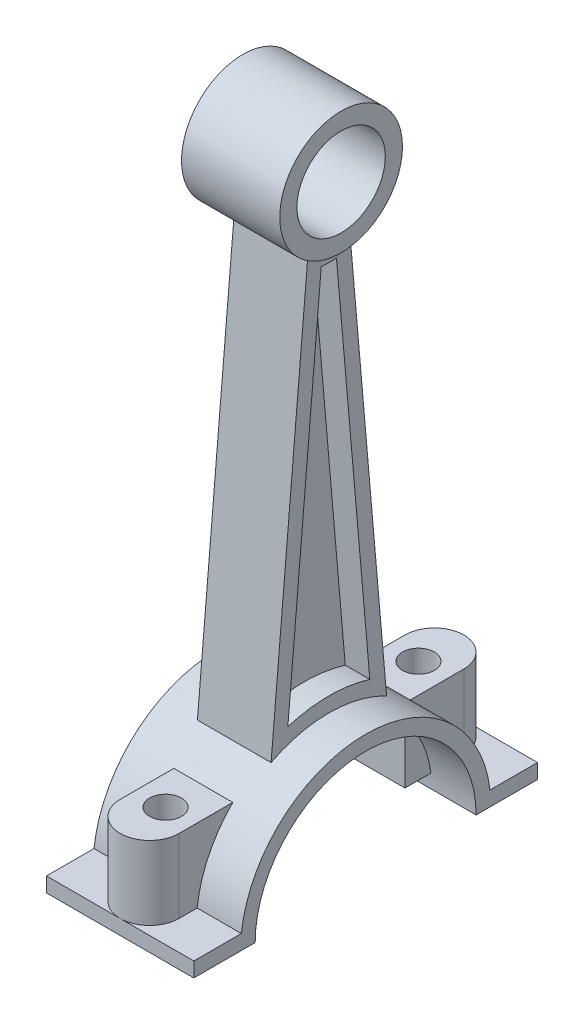
SolidWorks part; units mm, degrees
ref_plane "Front Plane" through (0, 0, 0) normal (0, 0, 1) x (1, 0, 0)
ref_plane "Top Plane" through (0, 0, 0) normal (0, 1, 0) x (1, 0, 0)
ref_plane "Right Plane" through (0, 0, 0) normal (1, 0, 0) x (0, 0, -1)
sketch "Sketch3" plane through (0, 0, 0) normal (1, 0, 0) x (0, 0, -1)
  line L0 (0, 42.5703) -> (0, -198.2297) construction
  line L1 (22.5, -77.8297) -> (35, -77.8297)
  line L2 (-22.5, -77.8297) -> (-35, -77.8297)
  line L3 (25.3229, -74.8297) -> (35, -74.8297)
  line L4 (-25.3229, -74.8297) -> (-35, -74.8297)
  line L5 (-35, -74.8297) -> (-35, -77.8297)
  line L6 (35, -74.8297) -> (35, -77.8297)
  line L7 (-4.2373, 30.8104) -> (-11.7627, -55.2048)
  line L8 (4.2373, 30.8104) -> (11.7627, -55.2048)
  circle A0 centre (0, 42.5703) radius 9
  circle A1 centre (0, 42.5703) radius 12.5
  arc A2 (22.5, -77.8297) -> (-22.5, -77.8297) centre (0, -77.8297) ccw
  arc A3 (25.3229, -74.8297) -> (-25.3229, -74.8297) centre (0, -77.8297) ccw
  point P17 (-8, -12.1972)
  dimension "D1" = 18
  dimension "D2" = 25
  dimension "D4" = 45
  dimension "D3" = 120.4
  dimension "D5" = 35
  dimension "D7" = 8
  dimension "D8" = 5
  dimension "D6" = 3
extrude "Boss-Extrude2" add sketch "Sketch3" along normal mid plane 20 contours A0 A1 region at (0, 30.4238, 0)
extrude "Boss-Extrude3" add sketch "Sketch3<4>" along normal mid plane 30 separate body contours L0 A3 L4 L5 L2 A2 | A3 L0 A2 L1 L6 L3 region at (0, -53.4796, -5.9516) region at (0, -53.8297, 0.433)
sketch "Sketch3<4>" plane through (0, 0, 0) normal (1, 0, 0) x (0, 0, -1) same geometry as "Sketch3"
extrude "Boss-Extrude4" add sketch "Sketch3<5>" along normal mid plane 15 contours L0 A1 L7 A3 | A1 L0 A3 L8 region at (0, -17.889, -4.2983) region at (0, -17.889, 4.2983)
sketch "Sketch3<5>" plane through (0, 0, 0) normal (1, 0, 0) x (0, 0, -1) same geometry as "Sketch3"
sketch "Sketch4" plane through (0, -74.8297, 0) normal (0, 1, 0) x (1, 0, 0)
  line L0 (0, 35) -> (0, 11.7617) construction
  line L1 (15, 35) -> (-15, 35) construction
  line L3 (-4.0913, 35) -> (4.0913, 35)
  line L4 (-6, 29) -> (-6, 17)
  line L5 (-6, 17) -> (6, 17)
  line L6 (6, 29) -> (6, 17)
  arc A1 (6, 29) -> (-6, 29) centre (0, 29) ccw
  line M7 (-15, 25.3229) -> (15, 25.3229)
  dimension "D1" = 6
  dimension "D2" = 12
extrude "Boss-Extrude5" add sketch "Sketch4" along normal blind 15 contours L0 A1 L4 M7 | A1 L0 L6 M7 | L0 L5 L6 M7 | L0 L4 L5 M7 region at (2.7453, -74.8297, -29.6245) region at (-2.7453, -74.8297, -29.6245) region at (3, -74.8297, -21.1615) region at (-3, -74.8297, -21.1615)
sketch "Sketch5" plane through (0, -59.8297, 0) normal (0, 1, 0) x (1, 0, 0)
  circle A0 centre (0, 25.75) radius 3.25
  dimension "D1" = 6.5
extrude "Cut-Extrude1" cut sketch "Sketch5" against normal through all
mirror "Mirror1" about plane through (0, 0, 0) normal (0, 0, 1) of "Cut-Extrude1", "Boss-Extrude5"
sketch "Sketch9" plane through (-7.5, 0, 0) normal (-1, 0, 0) x (0, 0, 1)
  line L0 (-1.5463, 27.1476) -> (-8.3465, -50.5793)
  line L1 (8.3465, -50.5793) -> (1.5463, 27.1476)
  line L2 (11.7627, -55.2048) -> (4.2373, 30.8104)
  line L3 (-4.2373, 30.8104) -> (-11.7627, -55.2048)
  line L4 (11.7627, -55.2048) -> (4.2373, 30.8104)
  line L5 (-4.2373, 30.8104) -> (-11.7627, -55.2048)
  arc A0 (8.3465, -50.5793) -> (-8.3465, -50.5793) centre (0, -77.8297) ccw
  arc A1 (-1.5463, 27.1476) -> (1.5463, 27.1476) centre (0, 42.5703) ccw
  arc A2 (11.7627, -55.2048) -> (-11.7627, -55.2048) centre (0, -77.8297) ccw
  arc A3 (-4.2373, 30.8104) -> (4.2373, 30.8104) centre (0, 42.5703) ccw
  arc A4 (11.7627, -55.2048) -> (-11.7627, -55.2048) centre (0, -77.8297) ccw
  arc A5 (-4.2373, 30.8104) -> (4.2373, 30.8104) centre (0, 42.5703) ccw
  dimension "D1" = 0
  dimension "D2" = 3
extrude "Cut-Extrude3" cut sketch "Sketch9" against normal blind 5 contours A1 L0 A0 L1 region at (-7.5, -20.0855, 0)
mirror "Mirror2" about plane through (0, 0, 0) normal (1, 0, 0) of "Cut-Extrude3"
